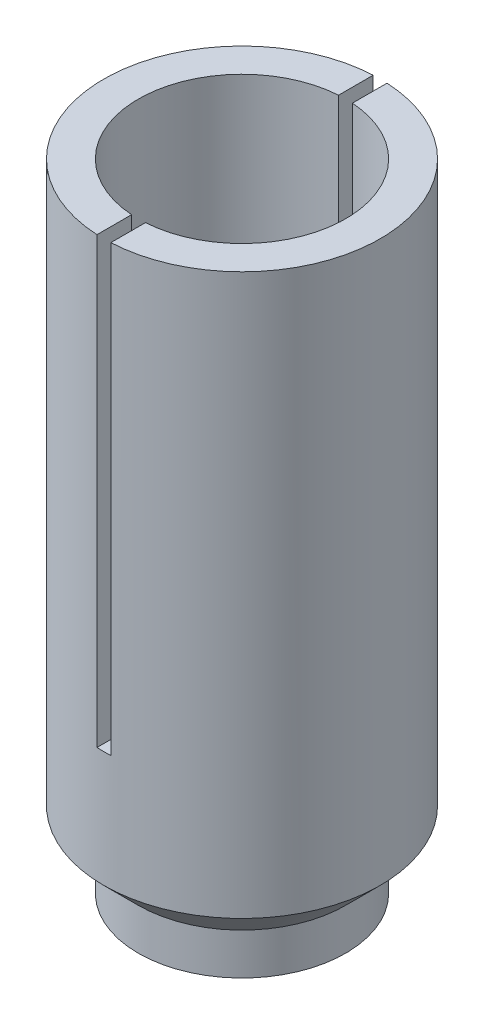
SolidWorks part; units mm, degrees
ref_plane "Front Plane" through (0, 0, 0) normal (0, 0, 1) x (1, 0, 0)
ref_plane "Top Plane" through (0, 0, 0) normal (0, 1, 0) x (1, 0, 0)
ref_plane "Right Plane" through (0, 0, 0) normal (1, 0, 0) x (0, 0, -1)
sketch "Sketch1" plane through (0, 0, 0) normal (0, 1, 0) x (1, 0, 0)
  circle A0 centre (0, 0) radius 2.5
  circle A1 centre (0, 0) radius 1.25 construction
  circle A2 centre (0, 0) radius 3.75
  dimension "D1" = 2.5
  dimension "D2" = 5
  dimension "D3" = 7.5
extrude "Boss-Extrude1" add sketch "Sketch1" along normal blind 3
sketch "Sketch2" plane through (0, 3, 0) normal (0, 1, 0) x (1, 0, 0)
  circle A0 centre (0, 0) radius 5
  circle A1 centre (0, 0) radius 1.25
  dimension "D1" = 2.5
  dimension "D2" = 10
extrude "Boss-Extrude2" add sketch "Sketch2" along normal blind 20
sketch "Sketch3" plane through (0, 23, 0) normal (0, 1, 0) x (1, 0, 0)
  circle A0 centre (0, 0) radius 3.75
  dimension "D1" = 7.5
extrude "Cut-Extrude1" cut sketch "Sketch3" against normal blind 19
chamfer "Chamfer1" distance 1.5 angle 45 2 edges at (0, 3, 3.75) (0, 4, 3.75)
sketch "Sketch4" plane through (0, 0, 0) normal (0, 0, 1) x (1, 0, 0)
  line L0 (3.75, 23) -> (-3.75, 23) construction
  line L1 (-0.25, 39.0593) -> (0.25, 39.0593)
  line L2 (-0.25, 39.0593) -> (-0.25, 6.9407)
  line L3 (-0.25, 6.9407) -> (0.25, 6.9407)
  line L4 (0.25, 39.0593) -> (0.25, 6.9407)
  line L5 (-0.25, 39.0593) -> (0.25, 6.9407) construction
  line L6 (-0.25, 6.9407) -> (0.25, 39.0593) construction
  point P0 (0, 23)
  dimension "D1" = 0.5
extrude "Cut-Extrude2" cut sketch "Sketch4" against normal through all and the other way through all
